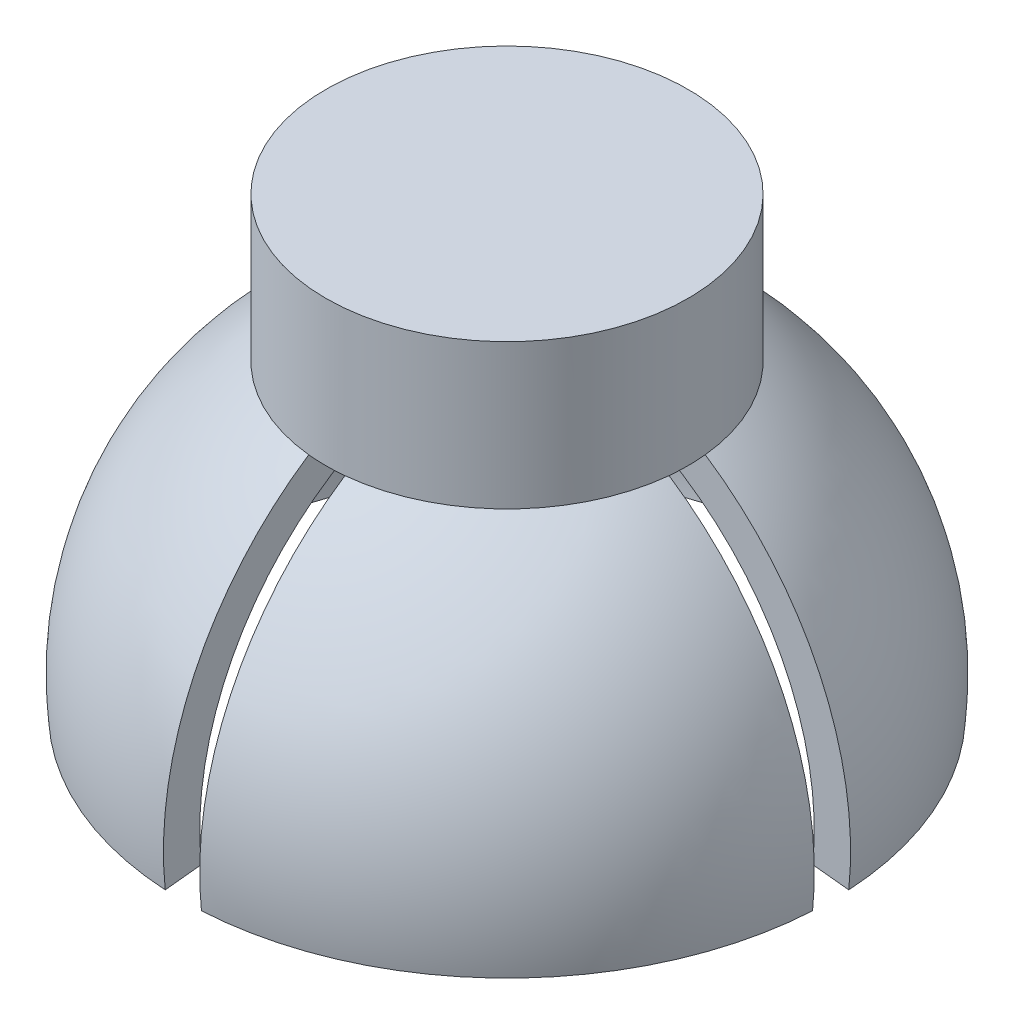
SolidWorks part; units mm, degrees
ref_plane "Front Plane" through (0, 0, 0) normal (0, 0, 1) x (1, 0, 0)
ref_plane "Top Plane" through (0, 0, 0) normal (0, 1, 0) x (1, 0, 0)
ref_plane "Right Plane" through (0, 0, 0) normal (1, 0, 0) x (0, 0, -1)
sketch "Sketch1" plane through (0, 0, 0) normal (0, 0, 1) x (1, 0, 0)
  line L1 (0, 5.7417) -> (0, 4)
  line L4 (3.9781, -0.4181) -> (4.4753, -0.4704)
  line L5 (0, 0) -> (3.8805, 0) construction
  line L6 (0, 0) -> (3.9781, -0.4181) construction
  line L9 (2.5, 5.7417) -> (0, 5.7417)
  line L10 (2.5, 3.7417) -> (2.5, 5.7417)
  arc A0 (3.9781, -0.4181) -> (0, 4) centre (0, 0) ccw
  arc A1 (4.4753, -0.4704) -> (2.5, 3.7417) centre (0, 0) ccw
  dimension "D1" = 4
  dimension "D2" = 9
  dimension "D3" = 6
  dimension "D4" = 2.5
  dimension "D5" = 2
revolve "Revolve1" add sketch "Sketch1" angle 360 about L1
sketch "Sketch2" plane through (0, 0, 0) normal (0, 0, 1) x (1, 0, 0)
  line L0 (-0.25, -0.4704) -> (-0.25, 3.7417)
  line L1 (-0.25, -0.4704) -> (0.25, -0.4704)
  line L2 (-0.25, 3.7417) -> (0.25, 3.7417)
  line L3 (0.25, -0.4704) -> (0.25, 3.7417)
  line L4 (4.4753, -0.4704) -> (-4.4753, -0.4704) construction
  line L5 (-2.5, 3.7417) -> (2.5, 3.7417) construction
  point P6 (0, 3.7417)
  dimension "D1" = 0.5
extrude "Cut-Extrude1" cut sketch "Sketch2" against normal blind 10
pattern_circular "CirPattern1" count 4 over 360 about axis through (0, -0.4704, 0) along (0, 1, 0) of "Cut-Extrude1"
